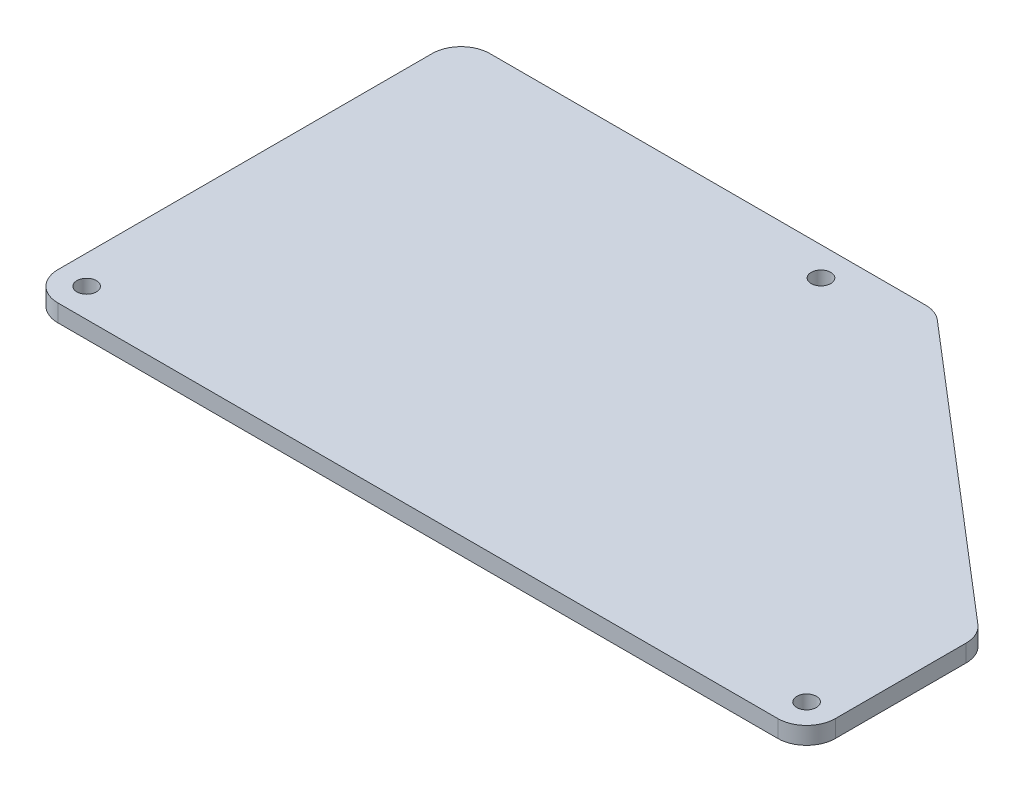
SolidWorks part; units mm, degrees
ref_plane "Front" through (0, 0, 0) normal (0, 0, 1) x (1, 0, 0)
ref_plane "Top" through (0, 0, 0) normal (0, 1, 0) x (1, 0, 0)
ref_plane "Right" through (0, 0, 0) normal (1, 0, 0) x (0, 0, -1)
sketch "Esquisse1" plane through (0, 0, 0) normal (0, 1, 0) x (1, 0, 0)
  line L0 (-67.5, 0) -> (67.5, 0)
  line L1 (0, 0) -> (67.5, 0) construction
  line L2 (0, 0) -> (0, 75) construction
  line L3 (0, 75) -> (67.5, 75) construction
  line L4 (67.5, 0) -> (67.5, 75) construction
  line L5 (67.5, 0) -> (67.5, 30)
  line L6 (67.5, 30) -> (15, 75)
  line L7 (15, 75) -> (-15, 75)
  line L9 (-67.5, 0) -> (-67.5, 30)
  line L10 (-67.5, 30) -> (-67.5, 75)
  line L11 (-67.5, 75) -> (-15, 75)
  dimension "D1" = 67.5
  dimension "D2" = 30
  dimension "D3" = 15
  dimension "D4" = 75
extrude "Boss.-Extru.1" add sketch "Esquisse1" along normal blind 3
fillet "Congé1" radius 5 5 edges at (-67.5, 1.5, 0) (15, 1.5, -75) (67.5, 1.5, -30) (67.5, 1.5, 0) (-67.5, 1.5, -75)
sketch "Esquisse2" plane through (0, 3, 0) normal (0, 1, 0) x (1, 0, 0)
  line L0 (-62.5, 0) -> (62.5, 0) construction
  line L1 (67.5, 5) -> (67.5, 27.7003) construction
  circle A0 centre (-62.5, 5) radius 1
  circle A1 centre (62.5, 5) radius 1
  circle A2 centre (0, 70) radius 1
  dimension "D4" = 2
  dimension "D5" = 2
  dimension "D6" = 2
  dimension "D1" = 62.5
  dimension "D2" = 62.5
  dimension "D3" = 65
  dimension "D7" = 5
  dimension "D8" = 5
  dimension "D9" = 67.5
extrude "Enlèv. mat.-Extru.2" cut sketch "Esquisse2" against normal up to surface (3 mm away) up to face at (3.2296, 0, -36.244)
hole_wizard "Dégagement M31" positions "Esquisse3" profile "Esquisse4" hole size "M3" standard "ISO"
sketch "Esquisse3" plane through (0, 3, 0) normal (0, 1, 0) x (1, 0, 0)
  point P0 (-62.5, 5)
  point P3 (62.5, 5)
  point P6 (0, 70)
sketch "Esquisse4" plane through (-62.5, 3, -5) normal (1, 0, 0) x (0, 0, 1)
  line L0 (0, 0) -> (0, 11.0215)
  line L1 (0, 11.0215) -> (1.7, 10)
  line L2 (1.7, 10) -> (1.7, 0)
  line L5 (1.7, 0) -> (0, 0)
  line L10 (0, 11.0215) -> (-1.7, 10) construction
  line L11 (0, -6.35) -> (0, 107.95) construction
  dimension "Diamètre du perçage" = 3.4
  dimension "Profondeur du perçage" = 10
  dimension "Angle de pointe" = 118
equation "\"D1@Esquisse1\"=135/2"
equation "\"D1@Esquisse2\"=125/2"
